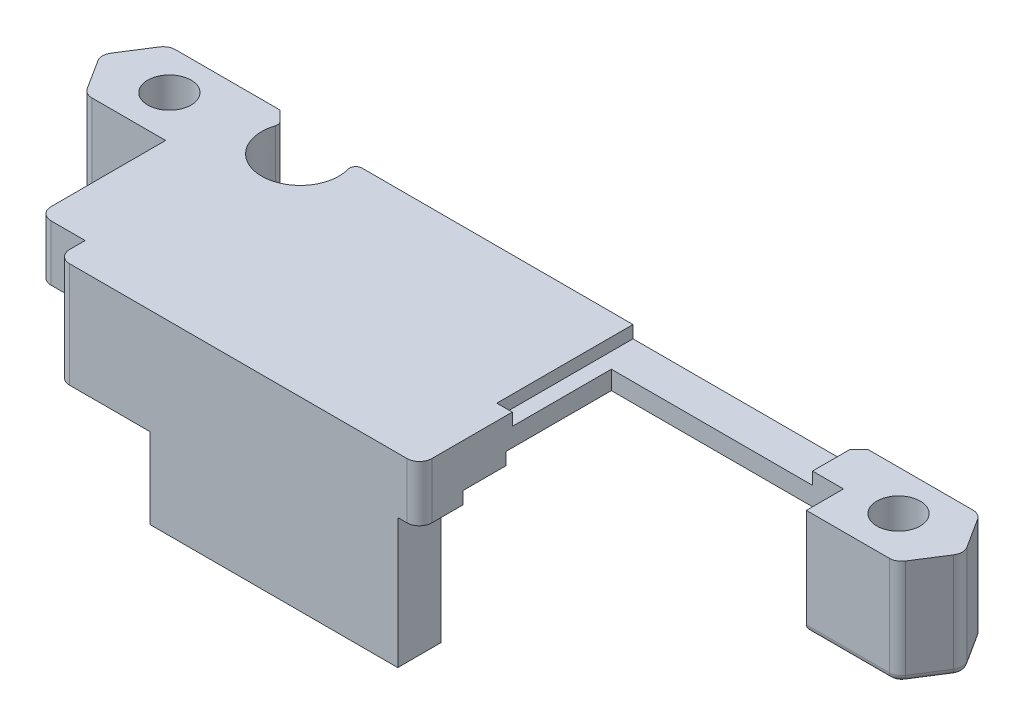
SolidWorks part; units mm, degrees
ref_plane "Front Plane" through (0, 0, 0) normal (0, 0, 1) x (1, 0, 0)
ref_plane "Top Plane" through (0, 0, 0) normal (0, 1, 0) x (1, 0, 0)
ref_plane "Right Plane" through (0, 0, 0) normal (1, 0, 0) x (0, 0, -1)
sketch "Sketch1" plane through (0, 0, 0) normal (0, 1, 0) x (1, 0, 0)
  line L0 (-9.2, 0) -> (9.2, 0)
  line L1 (-9, -6.5) -> (-9, -7.4)
  line L3 (-10.5, -2.4) -> (-10.5, -6.5)
  line L4 (-10.5, -6.5) -> (-9, -6.5)
  line L5 (0, 13.9813) -> (0, -13.9813) construction
  line L7 (-9.2, 0) -> (-9.5, 0.3)
  line L8 (-9.5, 0.3) -> (-13.1, 0.3)
  line L9 (-13.1, 0.3) -> (-13.96, -1.05)
  line L10 (-13.96, -1.05) -> (-13.1, -2.4)
  line L11 (-13.1, -2.4) -> (-10.5, -2.4)
  line L12 (-13.1, 0.3) -> (-13.1, -2.4) construction
  line L15 (13.1, 0.3) -> (13.1, -2.4) construction
  line L16 (10.2, -2.4) -> (10.2, -7.4)
  line L18 (13.1, -2.4) -> (10.2, -2.4)
  line L19 (13.96, -1.05) -> (13.1, -2.4)
  line L20 (13.1, 0.3) -> (13.96, -1.05)
  line L21 (9.5, 0.3) -> (13.1, 0.3)
  line L22 (9.2, 0) -> (9.5, 0.3)
  line L23 (10.2, -7.4) -> (-9, -7.4)
  circle A0 centre (-11.7782, -0.9999) radius 0.7
  circle A1 centre (11.7782, -0.9999) radius 0.7
  point P1 (0, 0)
  point P14 (-13.1, -1.05)
  point P28 (0, -7.3)
  point P33 (0, 0)
  dimension "D9" = 1.4
  dimension "D1" = 2.7
  dimension "D2" = 115
  dimension "D3" = 0.3
  dimension "D4" = 0.3
  dimension "D5" = 3.6
  dimension "D6" = 0.9
  dimension "D7" = 1.5
  dimension "D8" = 1.3
  dimension "D10" = 11.7782
  dimension "D11" = 0.9999
  dimension "D12" = 4.1
  dimension "D13" = 9.2
  dimension "D14" = 1
extrude "Boss-Extrude1" add sketch "Sketch1" along normal blind 1.8
sketch "Sketch2" plane through (0, 0, 0) normal (0, -1, 0) x (1, 0, 0)
  line L3 (2, 7.4) -> (2, 6)
  line L13 (-10.5, 2.4) -> (-10.5, 6.5) construction
  line L15 (-9, 7.4) -> (10.2, 7.4) construction
  line L16 (2, 7.4) -> (-9, 7.4)
  line L17 (-9, 7.4) -> (-9, 6)
  line L24 (-9.2, 0) -> (-9.5, -0.3) construction
  line L25 (-9.5, -0.3) -> (-13.1, -0.3) construction
  line L26 (-13.1, -0.3) -> (-13.96, 1.05) construction
  line L27 (-13.96, 1.05) -> (-13.1, 2.4) construction
  line L28 (-13.1, 2.4) -> (-10.5, 2.4) construction
  line L29 (-9.2, 0) -> (-9.5, -0.3)
  line L30 (-9.5, -0.3) -> (-13.1, -0.3)
  line L31 (-13.1, -0.3) -> (-13.96, 1.05)
  line L32 (-13.96, 1.05) -> (-13.1, 2.4)
  line L33 (-13.1, 2.4) -> (-10.5, 2.4)
  line L34 (-9.2, 0) -> (-9.2, 0.5024)
  line L38 (13.96, 1.05) -> (13.1, -0.3) construction
  line L39 (13.1, 2.4) -> (13.96, 1.05) construction
  line L40 (10.2, 2.4) -> (13.1, 2.4) construction
  line L45 (13.96, 1.05) -> (13.1, -0.3)
  line L46 (13.1, 2.4) -> (13.96, 1.05)
  line L47 (10.2, 2.4) -> (13.1, 2.4)
  line L51 (2, 6) -> (-9, 6)
  line L53 (-10.5, 2.4) -> (-10.5, 1.7)
  line L54 (-10.5, 1.7) -> (-9.2, 0.5024)
  line L57 (10.2, -0.3) -> (10.2, 2.4)
  line L58 (10.2, 7.4) -> (10.2, 2.4) construction
  line L59 (13.1, -0.3) -> (9.5, -0.3) construction
  line L60 (13.1, -0.3) -> (10.2, -0.3)
  circle A0 centre (-11.7782, 0.9999) radius 0.7 construction
  circle A1 centre (-11.7782, 0.9999) radius 0.7
  circle A2 centre (11.7782, 0.9999) radius 0.7 construction
  circle A3 centre (11.7782, 0.9999) radius 0.7
  dimension "D1" = 11
  dimension "D2" = 1.4
  dimension "D7" = 0.5024
  dimension "D8" = 0.7
extrude "Boss-Extrude2" add sketch "Sketch2" along normal blind 1.6
sketch "Sketch9" plane through (0, 0, 0) normal (0, -1, 0) x (1, 0, 0)
  line L0 (10.2, 7.4) -> (10.2, 1.2)
  line L1 (10.2, 1.2) -> (2.7, 1.2)
  line L3 (2, 7.4) -> (10.2, 7.4) construction
  line L4 (2.7, 7.4) -> (10.2, 7.4)
  line L11 (2.7, 7.4) -> (2.7, 1.2)
  dimension "D2" = 7.5
  dimension "D3" = 6.2
extrude "Cut-Extrude6" cut sketch "Sketch9" against normal blind 3
sketch "Sketch10" plane through (0, -1.6, 0) normal (0, -1, 0) x (1, 0, 0)
  line L0 (2, 6) -> (2, 7.4)
  line L1 (2, 7.4) -> (-6, 7.4)
  line L2 (2, 7.4) -> (-9, 7.4) construction
  line L3 (-6, 7.4) -> (-6, 6)
  line L4 (2, 6) -> (-9, 6) construction
  line L5 (-6, 6) -> (2, 6)
  dimension "D1" = 8
extrude "Boss-Extrude3" add sketch "Sketch10" along normal blind 2.6
sketch "Sketch11" plane through (0, 0, 0) normal (0, -1, 0) x (1, 0, 0)
  line L0 (2.7, 1) -> (2.7, 6)
  line L1 (2.7, 7.4) -> (2.7, 1.2) construction
  line L2 (2.7, 6) -> (-9.7402, 6)
  line L3 (-9.7402, 6) -> (-9.7402, 1)
  line L4 (-9.7402, 1) -> (2.7, 1)
  line L5 (-6, 6) -> (2, 6) construction
  line L6 (-10.5, 1.7) -> (-9.2, 0.5024) construction
  point P8 (-9.7412, 1.001)
  dimension "D2" = 5
extrude "Cut-Extrude7" cut sketch "Sketch11" against normal blind 0.4
sketch "Sketch12" plane through (0, 0.4, 0) normal (0, -1, 0) x (1, 0, 0)
  line L0 (2.7, 1) -> (2.7, 4.6)
  line L1 (2.7, 1.2) -> (2.7, 6) construction
  line L2 (2.7, 4.6) -> (-9.7402, 4.6)
  line L3 (-9.7402, 6) -> (-9.7402, 1) construction
  line L4 (-9.7402, 4.6) -> (-9.7402, 1)
  line L5 (-9.7402, 1) -> (2.7, 1)
  dimension "D1" = 3.6
extrude "Cut-Extrude8" cut sketch "Sketch12" against normal blind 0.4
sketch "Sketch13" plane through (0, 0.8, 0) normal (0, -1, 0) x (1, 0, 0)
  line L0 (-5, 3.8) -> (-2.4, 3.8)
  line L1 (-2.4, 3.8) -> (-2.4, 5.2)
  line L2 (-2.4, 5.2) -> (-5, 5.2)
  line L3 (-5, 5.2) -> (-5, 3.8)
  line L4 (2.7, 6) -> (-9.7402, 6) construction
  line L5 (-6, 7.4) -> (-6, 6) construction
  dimension "D1" = 0.8
  dimension "D2" = 1
  dimension "D3" = 2.6
  dimension "D4" = 1.4
extrude "Boss-Extrude4" add sketch "Sketch13" along normal blind 4.8
fillet "Fillet1" radius 0.4 9 edges at (-10.5, 0.9, 6.5) (-9, 0.1, 7.4) (2.7, 0.9, 7.4) (13.1, 0.1, -0.3) (13.96, 0.1, 1.05) (13.1, 0.1, 2.4) (-13.1, 0.1, -0.3) (-13.96, 0.1, 1.05) (-13.1, 0.1, 2.4)
chamfer "Chamfer1" distance 0.8 angle 45 1 edges at (6.45, 0, 1.2)
sketch "Sketch14" plane through (0, 0, 0) normal (0, 0, -1) x (-1, 0, 0)
  line L0 (-9.2, 1.8) -> (-9.2, 1.4)
  line L1 (-9.2, 1.8) -> (-9.2, 0) construction
  line L2 (-9.2, 1.4) -> (-2.2, 1.4)
  line L3 (-2.2, 1.4) -> (-2.2, 1.8)
  line L4 (-9.2, 1.8) -> (9.2, 1.8) construction
  line L5 (-2.2, 1.8) -> (-9.2, 1.8)
  dimension "D1" = 7
  dimension "D2" = 0.4
extrude "Cut-Extrude9" cut sketch "Sketch14" against normal blind 4.4
sketch "Sketch15" plane through (0, 1.8, 0) normal (0, 1, 0) x (1, 0, 0)
  line L0 (-9.2, 0) -> (-9.2, -6.5) construction
  line L1 (-10.1, -6.5) -> (-9, -6.5) construction
  line L2 (2.2, 0) -> (-9.2, 0) construction
  circle A0 centre (-7.95, -0.6) radius 1.25
  dimension "D1" = 2.5
  dimension "D2" = 0.6
extrude "Cut-Extrude10" cut sketch "Sketch15" against normal blind 10
fillet "Fillet2" radius 0.2 24 edges at (-11.6903, -1.6, 2.4) (-13.0729, -1.6, 2.3507) (-13.5205, -1.6, 1.7399) (-13.8858, -1.6, 1.05) (-11.1903, -1.6, -0.3) (-13.0729, -1.6, -0.2507) (11.5403, -1.6, -0.3) (13.0729, -1.6, -0.2507) (13.5205, -1.6, 0.3601) (13.8858, -1.6, 1.05) (11.5403, -1.6, 2.4) (13.0729, -1.6, 2.3507) (-5, -1.8, 5.2) (-5, -1.6, 3.8) (-2.4, -1.8, 5.2) (-2.4, -1.6, 3.8) (-10.5, -1.6, 2.05) (-9.85, -1.6, 1.1012) (-9.2, -1.6, 0.2512) (-13.5205, -1.6, 0.3601) (10.2, -1.6, 1.05) (13.5205, -1.6, 1.7399) (-6.8534, 0.9, 0) (-9.0466, 0.9, 0)
